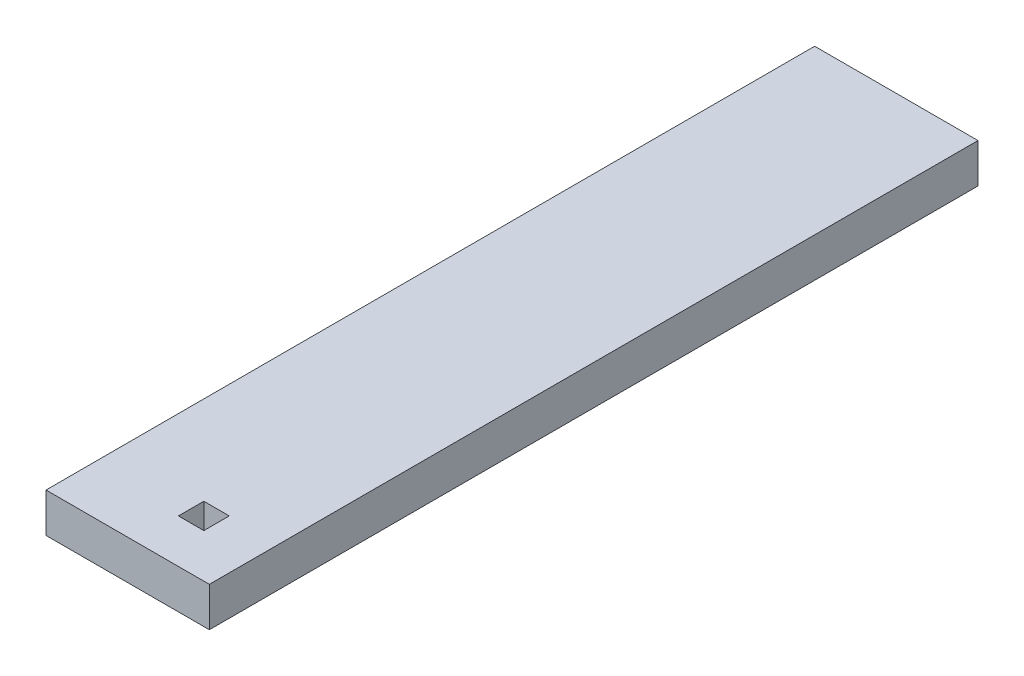
SolidWorks part; units mm, degrees
material "Acrylic (Medium-high impact)"
ref_plane "Front Plane" through (0, 0, 0) normal (0, 0, 1) x (1, 0, 0)
ref_plane "Top Plane" through (0, 0, 0) normal (0, 1, 0) x (1, 0, 0)
ref_plane "Right Plane" through (0, 0, 0) normal (1, 0, 0) x (0, 0, -1)
sketch "Sketch1" plane through (0, 0, 0) normal (0, 1, 0) x (1, 0, 0)
  line L0 (0, -26.4442) -> (0, 0) construction
  line L1 (5, -31) -> (-5, -31)
  line L2 (5, -31) -> (5, 31)
  line L3 (5, 31) -> (-5, 31)
  line L4 (-5, -31) -> (-5, 31)
  line L5 (5, -31) -> (-5, 31) construction
  line L6 (5, 31) -> (-5, -31) construction
  line L7 (-1.025, -25.4192) -> (1.025, -25.4192)
  line L8 (-1.025, -25.4192) -> (-1.025, -27.4692)
  line L9 (-1.025, -27.4692) -> (1.025, -27.4692)
  line L10 (1.025, -25.4192) -> (1.025, -27.4692)
  line L11 (-1.025, -25.4192) -> (1.025, -27.4692) construction
  line L12 (-1.025, -27.4692) -> (1.025, -25.4192) construction
  point P0 (0, 0)
  point P6 (0, -26.4442)
  dimension "D1" = 10
  dimension "D2" = 62
  dimension "D3" = 2.05
  dimension "D4" = 57.4442
extrude "Boss-Extrude1" add sketch "Sketch1" along normal blind 3.175 contours L1 L2 L3 L4 L7 L10 L9 L8 | L4 region at (0, 0, -0.1805)
sketch "Sketch2" plane through (0, 3.175, 0) normal (0, 1, 0) x (1, 0, 0)
  line L5 (5, -31) -> (-5, -31) construction
  line L6 (-5, 31) -> (-8.175, 31)
  line L7 (-5, 31) -> (-5, -31)
  line L8 (-5, -31) -> (-8.175, -31)
  line L9 (-8.175, 31) -> (-8.175, -31)
  dimension "D1" = 3.175
extrude "Boss-Extrude2" add sketch "Sketch2" against normal up to surface (3.175 mm away) up to face at (0, 0, 0)
equation "\"bottomThickness\"= .220in"
equation "\"wallThickness\"= .125in"
equation "\"D1@Boss-Extrude1\"=\"wallThickness\""
equation "\"D1@Sketch2\"=\"wallThickness\""
